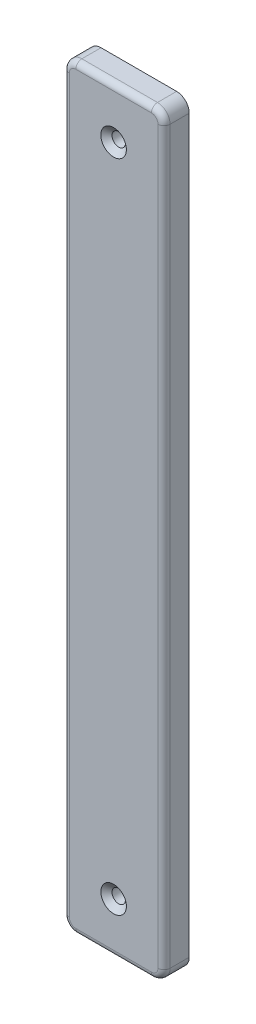
SolidWorks part; units mm, degrees
material "Teak"
ref_plane "Front" through (0, 0, 0) normal (0, 0, 1) x (1, 0, 0)
ref_plane "Top" through (0, 0, 0) normal (0, 1, 0) x (1, 0, 0)
ref_plane "Right" through (0, 0, 0) normal (1, 0, 0) x (0, 0, -1)
sketch "Sketch1" plane through (0, 0, 0) normal (0, 0, 1) x (1, 0, 0)
  line L0 (0, 190.5) -> (0, -190.5) construction
  line L1 (25.4, -190.5) -> (-25.4, -190.5)
  line L2 (25.4, -190.5) -> (25.4, 190.5)
  line L3 (-25.4, 190.5) -> (25.4, 190.5)
  line L4 (-25.4, 190.5) -> (-25.4, -190.5)
  dimension "D1" = 381
  dimension "D3" = 50.8
extrude "Base-Extrude" add sketch "Sketch1" along normal blind 12.7
sketch "Sketch2" plane through (0, 0, 12.7) normal (0, 0, 1) x (1, 0, 0)
  line L0 (0, 0) -> (71.1, 0) construction
  line L1 (0, 190.5) -> (0, -190.5) construction
  line L2 (-25.4, 190.5) -> (25.4, 190.5) construction
  line L3 (25.4, -190.5) -> (-25.4, -190.5) construction
  point P0 (0, -165.1)
  point P2 (0, 165.1)
  dimension "D1" = 330.2
hole_wizard "CSK for 1/4 Flat Head Machine Screw (100)1" positions "Sketch5" profile "Sketch4" countersink size "1/4" standard "Ansi Inch" end condition through all
sketch "Sketch5" plane through (0, 0, 12.7) normal (0, 0, 1) x (1, 0, 0)
  point P0 (0, 165.1)
  point P1 (0, -165.1)
sketch "Sketch4" plane through (0, 165.1, 12.7) normal (1, 0, 0) x (0, -1, 0)
  line L0 (0, 0) -> (0, 12.7)
  line L1 (0, 12.7) -> (3.3782, 12.7)
  line L2 (3.3782, 12.7) -> (3.3782, 2.5682)
  line L3 (3.3782, 2.5682) -> (6.4389, 0)
  line L5 (6.4389, 0) -> (0, 0)
  line L6 (-3.3782, 2.5682) -> (-6.4389, 0) construction
  line L11 (0, -6.35) -> (0, 107.95) construction
  dimension "Thru Hole Dia." = 6.7564
  dimension "Thru Hole Depth" = 12.7
  dimension "Near C'Sink Dia." = 12.8778
  dimension "Near C'Sink Angle" = 100
fillet "Fillet1" radius 6.35 4 edges at (25.4, -190.5, 6.35) (-25.4, -190.5, 6.35) (-25.4, 190.5, 6.35) (25.4, 190.5, 6.35)
fillet "Fillet2" radius 3.048 8 edges at (-23.5401, 188.6401, 12.7) (0, 190.5, 12.7) (23.5401, 188.6401, 12.7) (25.4, 0, 12.7) (23.5401, -188.6401, 12.7) (0, -190.5, 12.7) (-23.5401, -188.6401, 12.7) (-25.4, 0, 12.7)
